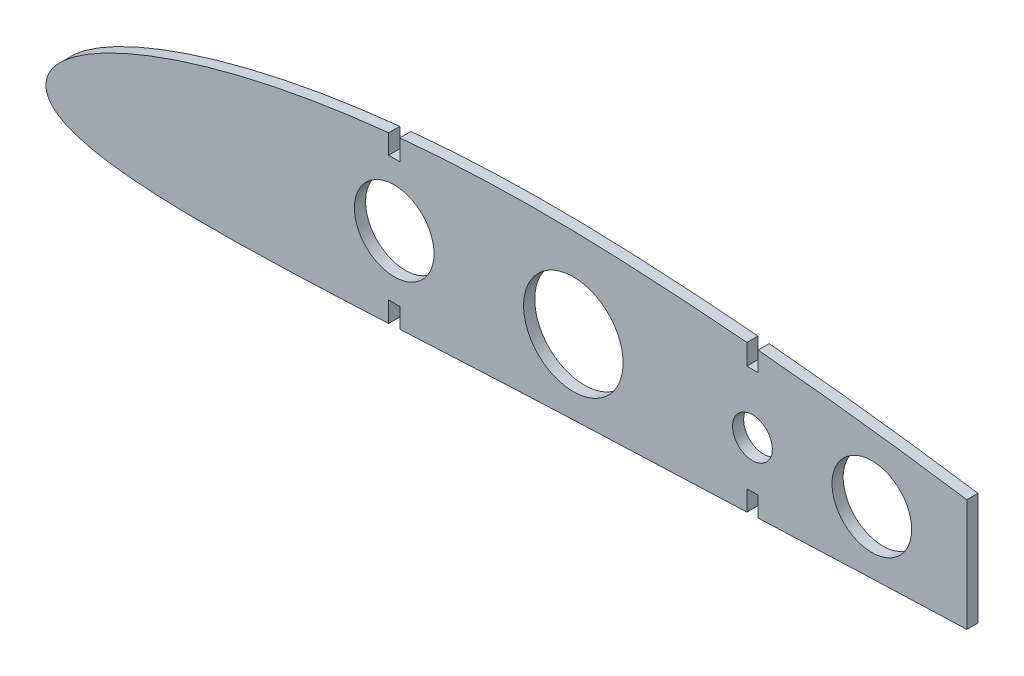
SolidWorks part; units mm, degrees
material "Фанера"
ref_plane "Front Plane" through (0, 0, 0) normal (0, 0, 1) x (1, 0, 0)
ref_plane "Top Plane" through (0, 0, 0) normal (0, 1, 0) x (1, 0, 0)
ref_plane "Right Plane" through (0, 0, 0) normal (1, 0, 0) x (0, 0, -1)
curve "Кривая1"
  spline degree 3 poles (0.0672, 0.87, 0) (0.0318, 0.5229, 0) (-0.0389, -0.1715, 0) (0.1092, -1.2382, 0) (0.4896, -2.2944, 0) (1.1401, -3.3111, 0) (2.0489, -4.255, 0) (3.2074, -5.1254, 0) (4.6283, -5.9301, 0) (6.3494, -6.6831, 0) (8.4416, -7.3951, 0) (11.0166, -8.0714, 0) (14.2364, -8.7104, 0) (18.3056, -9.2955, 0) (23.4194, -9.7901, 0) (29.6659, -10.1463, 0) (36.96, -10.3273, 0) (45.0764, -10.3268, 0) (53.7569, -10.166, 0) (62.8007, -9.8793, 0) (72.0812, -9.501, 0) (81.5234, -9.0613, 0) (91.0729, -8.586, 0) (100.6751, -8.0976, 0) (110.2799, -7.6156, 0) (119.8547, -7.1553, 0) (129.405, -6.7269, 0) (138.957, -6.3448, 0) (148.5363, -5.9896, 0) (158.1569, -5.6043, 0) (167.8102, -5.2124, 0) (177.4834, -4.8161, 0) (187.1542, -4.4222, 0) (196.8146, -4.0353, 0) (206.4608, -3.6595, 0) (216.0936, -3.2979, 0) (225.7151, -2.9531, 0) (235.3272, -2.6273, 0) (244.9322, -2.3221, 0) (254.532, -2.0389, 0) (264.1285, -1.7785, 0) (273.7233, -1.5416, 0) (283.3173, -1.3281, 0) (292.9097, -1.138, 0) (302.4935, -0.971, 0) (312.041, -0.8264, 0) (321.4647, -0.7041, 0) (330.5223, -0.6041, 0) (338.7731, -0.5271, 0) (345.1826, -0.4754, 0) (348.7687, -0.4498, 0) (350, -0.441, 0) knots 0 0 0 0 0.002941 0.005884 0.009016 0.012365 0.016008 0.020037 0.024574 0.029784 0.035897 0.04324 0.052276 0.063635 0.077983 0.095698 0.11652 0.139661 0.164312 0.189919 0.216157 0.242838 0.269834 0.296993 0.324123 0.351139 0.378036 0.404946 0.431961 0.459078 0.486347 0.513641 0.540929 0.568176 0.59538 0.622543 0.649673 0.676775 0.703855 0.730919 0.757971 0.785018 0.812062 0.839103 0.866132 0.893099 0.919831 0.94581 0.969681 0.98959 1 1 1 1
curve "Кривая2"
  spline degree 3 poles (350, 0.441, 0) (348.8179, 0.763, 0) (345.4082, 1.6919, 0) (339.3479, 3.3017, 0) (331.5897, 5.3027, 0) (323.0919, 7.4172, 0) (314.2383, 9.538, 0) (305.2428, 11.6083, 0) (296.1874, 13.6076, 0) (287.1014, 15.5293, 0) (277.9952, 17.371, 0) (268.8733, 19.1314, 0) (259.7387, 20.8097, 0) (250.5935, 22.4048, 0) (241.4399, 23.9153, 0) (232.28, 25.3398, 0) (223.1162, 26.6763, 0) (213.9505, 27.9228, 0) (204.7856, 29.077, 0) (195.6239, 30.1359, 0) (186.4686, 31.0968, 0) (177.3222, 31.956, 0) (168.1915, 32.7096, 0) (159.08, 33.3545, 0) (150.0138, 33.8803, 0) (141.0375, 34.2978, 0) (132.1765, 34.5613, 0) (123.4183, 34.6361, 0) (114.7287, 34.5224, 0) (106.0927, 34.2174, 0) (97.5152, 33.7146, 0) (89.0056, 33.0092, 0) (80.5773, 32.0949, 0) (72.2481, 30.9667, 0) (64.0422, 29.6192, 0) (55.9942, 28.0495, 0) (48.1571, 26.2588, 0) (40.6145, 24.2587, 0) (33.4961, 22.0806, 0) (26.979, 19.788, 0) (21.2507, 17.4767, 0) (16.4367, 15.2539, 0) (12.5431, 13.2014, 0) (9.4652, 11.352, 0) (7.0472, 9.6945, 0) (5.1404, 8.1959, 0) (3.6289, 6.8198, 0) (2.4334, 5.5336, 0) (1.4978, 4.3133, 0) (0.8003, 3.1383, 0) (0.3021, 2.0031, 0) (0.1432, 1.2365, 0) (0.0672, 0.87, 0) knots 0 0 0 0 0.010162 0.029313 0.052012 0.076619 0.101948 0.127526 0.153184 0.178868 0.204558 0.230246 0.255926 0.281594 0.307246 0.332878 0.358485 0.384061 0.409603 0.435104 0.460559 0.485959 0.511303 0.536552 0.561723 0.586629 0.611085 0.635251 0.659272 0.683164 0.706922 0.730536 0.753983 0.777235 0.800246 0.822951 0.845237 0.866916 0.887662 0.906968 0.924203 0.938879 0.950932 0.960693 0.968647 0.975233 0.980795 0.985584 0.989782 0.993521 0.996902 1 1 1 1
sketch "Эскиз2" plane through (0, 0, 0) normal (0, 0, 1) x (1, 0, 0)
  line L1 (0, 0) -> (0, 59.698) construction
  line L2 (0, 0) -> (231.3768, 0) construction
  line L3 (87.5, 77.9689) -> (87.5, 51.797) construction
  line L5 (48.6093, 12.0313) -> (232.4701, 12.0313) construction
  line L10 (87.5, 32.8256) -> (87.5, -53.7006) construction
  line L12 (86.1, 32.6823) -> (86.1, 27.7856)
  line L13 (86.1, 27.7856) -> (88.9, 27.7856)
  line L14 (88.9, 32.963) -> (88.9, 27.7856)
  line L15 (87.5, 32.8256) -> (88.9, 27.7856) construction
  line L16 (86.1, 27.7856) -> (87.5, 32.8256) construction
  line L17 (177.5, 12.0313) -> (177.5, 39.9872) construction
  line L18 (177.5, 12.0313) -> (177.5, -23.4861) construction
  line L19 (176.1, 26.8829) -> (178.9, 26.8829)
  line L20 (176.1, 26.8829) -> (176.1, 32.0455)
  line L22 (178.9, 26.8829) -> (178.9, 31.7979)
  line L23 (176.1, 26.8829) -> (177.5, 31.9229) construction
  line L24 (177.5, 31.9229) -> (178.9, 26.8829) construction
  line L26 (86.1, -8.8326) -> (86.1, -3.7231)
  line L27 (86.1, -3.7231) -> (88.9, -3.7231)
  line L28 (88.9, -8.6933) -> (88.9, -3.7231)
  line L29 (87.5, -8.7631) -> (88.9, -3.7231) construction
  line L30 (86.1, -3.7231) -> (87.5, -8.7631) construction
  line L31 (231.3768, 25.4607) -> (231.3768, -2.7621)
  line L33 (176.1, -4.873) -> (176.1, 0.2242)
  line L34 (176.1, 0.2242) -> (178.9, 0.2242)
  line L35 (178.9, -4.7586) -> (178.9, 0.2242)
  line L36 (177.5, -4.8158) -> (178.9, 0.2242) construction
  line L37 (176.1, 0.2242) -> (177.5, -4.8158) construction
  circle A5 centre (87.5, 12.0313) radius 10
  circle A6 centre (177.5, 12.0313) radius 5
  circle A7 centre (132.5, 12.0313) radius 12.5
  circle A8 centre (207.5, 12.0313) radius 10
  spline S1 degree 3 poles (231.3768, 25.4607) (228.6231, 25.873) (222.8162, 26.7171) (213.9505, 27.9228) (204.7856, 29.077) (195.6239, 30.1359) (186.9965, 31.0414) (181.4212, 31.5705) (178.9, 31.7979) knots 0.335389 0.335389 0.335389 0.335389 0.358485 0.384061 0.409603 0.435104 0.460559 0.481556 0.481556 0.481556 0.481556
  spline S2 degree 3 poles (0.0672, 0.87) (0.0318, 0.5229) (-0.0389, -0.1715) (0.1092, -1.2382) (0.4896, -2.2944) (1.1401, -3.3111) (2.0489, -4.255) (3.2074, -5.1254) (4.6283, -5.9301) (6.3494, -6.6831) (8.4416, -7.3951) (11.0166, -8.0714) (14.2364, -8.7104) (18.3056, -9.2955) (23.4194, -9.7901) (29.6659, -10.1463) (36.96, -10.3273) (45.0764, -10.3268) (53.7569, -10.166) (62.8007, -9.8793) (72.0812, -9.501) (79.8719, -9.1382) (84.562, -8.9087) (86.1, -8.8326) knots 0 0 0 0 0.002941 0.005884 0.009016 0.012365 0.016008 0.020037 0.024574 0.029784 0.035897 0.04324 0.052276 0.063635 0.077983 0.095698 0.11652 0.139661 0.164312 0.189919 0.216157 0.242838 0.255856 0.255856 0.255856 0.255856
  spline S4 degree 3 poles (88.9, -8.6933) (89.6178, -8.6574) (93.5441, -8.4603) (100.6751, -8.0976) (110.2799, -7.6156) (119.8547, -7.1553) (129.405, -6.7269) (138.957, -6.3448) (148.5363, -5.9896) (158.1569, -5.6043) (167.3488, -5.2312) (173.3358, -4.986) (176.1, -4.873) knots 0.263757 0.263757 0.263757 0.263757 0.269834 0.296993 0.324123 0.351139 0.378036 0.404946 0.431961 0.459078 0.486347 0.509737 0.509737 0.509737 0.509737
  spline S5 degree 3 poles (86.1, 32.6823) (84.251, 32.489) (79.6181, 31.965) (72.2481, 30.9667) (64.0422, 29.6192) (55.9942, 28.0495) (48.1571, 26.2588) (40.6145, 24.2587) (33.4961, 22.0806) (26.979, 19.788) (21.2507, 17.4767) (16.4367, 15.2539) (12.5431, 13.2014) (9.4652, 11.352) (7.0472, 9.6945) (5.1404, 8.1959) (3.6289, 6.8198) (2.4334, 5.5336) (1.4978, 4.3133) (0.8003, 3.1383) (0.3021, 2.0031) (0.1432, 1.2365) (0.0672, 0.87) knots 0.738563 0.738563 0.738563 0.738563 0.753983 0.777235 0.800246 0.822951 0.845237 0.866916 0.887662 0.906968 0.924203 0.938879 0.950932 0.960693 0.968647 0.975233 0.980795 0.985584 0.989782 0.993521 0.996902 1 1 1 1
  spline S6 degree 3 poles (178.9, -4.7586) (181.653, -4.6463) (187.6262, -4.4033) (196.8146, -4.0353) (206.4608, -3.6595) (216.0936, -3.2979) (224.3975, -3.0003) (229.4906, -2.8257) (231.3768, -2.7621) knots 0.517634 0.517634 0.517634 0.517634 0.540929 0.568176 0.59538 0.622543 0.649673 0.665629 0.665629 0.665629 0.665629
  spline S7 degree 3 poles (176.1, 32.0455) (173.4606, 32.2744) (167.7863, 32.7382) (159.08, 33.3545) (150.0138, 33.8803) (141.0375, 34.2978) (132.1765, 34.5613) (123.4183, 34.6361) (114.7287, 34.5224) (106.0927, 34.2174) (97.4854, 33.7129) (91.7636, 33.2378) (88.9, 32.963) knots 0.489328 0.489328 0.489328 0.489328 0.511303 0.536552 0.561723 0.586629 0.611085 0.635251 0.659272 0.683164 0.706922 0.730783 0.730783 0.730783 0.730783
  point P1 (0, 0)
  point P2 (0, 0)
  point P3 (0, 0)
  point P4 (0, 0)
  point P14 (87.5, 32.8256)
  point P17 (87.5, -8.7631)
  point P26 (87.5, 32.8256)
  point P28 (177.5, 31.9229)
  point P35 (177.5, 31.9229)
  point P36 (87.5, -8.7631)
  point P42 (87.5, -8.7631)
  point P46 (177.5, -4.8158)
  point P49 (177.5, -4.8158)
  point P63 (231.3768, 25.4607)
  point P64 (231.3768, -2.7621)
  dimension "D5" = 20
  dimension "D8" = 10
  dimension "D10" = 25
  dimension "D12" = 20
  dimension "D3" = 87.5
  dimension "D6" = 41.5887
  dimension "D7" = 20.7944
  dimension "D9" = 90
  dimension "D11" = 45
  dimension "D13" = 30
  dimension "D14" = 2.8
  dimension "D15" = 1.4
  dimension "D16" = 5.04
  dimension "D17" = 2.8
  dimension "D18" = 1.4
  dimension "D19" = 5.04
  dimension "D20" = 2.8
  dimension "D21" = 5.04
  dimension "D22" = 1.4
  dimension "D23" = 2.8
  dimension "D24" = 5.04
  dimension "D25" = 1.4
extrude "Бобышка-Вытянуть1" add sketch "Эскиз2" along normal mid plane 2.8
equation "\"Thickness\"= 2.8"
equation "\"chord\"= 350"
equation "\"D3@Эскиз2\"=\"chord\"/4"
equation "\"D7@Эскиз2\"=\"D6@Эскиз2\"/2"
equation "\"D11@Эскиз2\"=\"D9@Эскиз2\"/2"
equation "\"D14@Эскиз2\"=\"Thickness\""
equation "\"D15@Эскиз2\"=\"D14@Эскиз2\"/2"
equation "\"D16@Эскиз2\"=\"Thickness\"*1.8"
equation "\"D17@Эскиз2\"=\"Thickness\""
equation "\"D18@Эскиз2\"=\"Thickness\"/2"
equation "\"D19@Эскиз2\"=\"Thickness\"*1.8"
equation "\"D20@Эскиз2\"=\"Thickness\""
equation "\"D21@Эскиз2\"=\"Thickness\"*1.8"
equation "\"D22@Эскиз2\"=\"Thickness\"/2"
equation "\"D23@Эскиз2\"=\"Thickness\""
equation "\"D24@Эскиз2\"=\"Thickness\"*1.8"
equation "\"D25@Эскиз2\"=\"Thickness\"/2"
